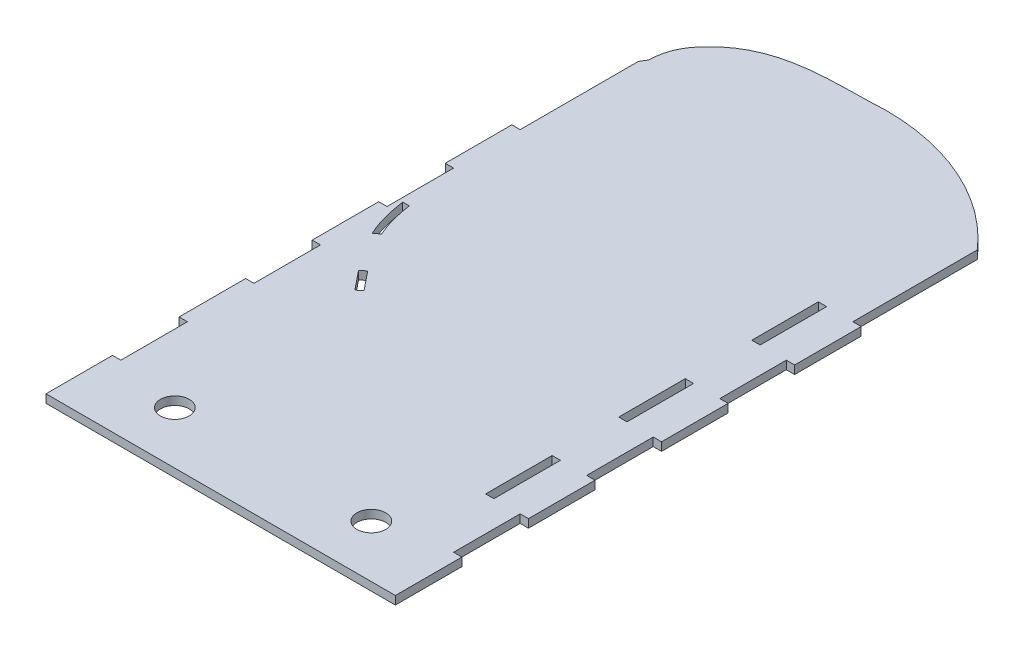
SolidWorks part; units mm, degrees
ref_plane "Front Plane" through (0, 0, 0) normal (0, 0, 1) x (1, 0, 0)
ref_plane "Top Plane" through (0, 0, 0) normal (0, 1, 0) x (1, 0, 0)
ref_plane "Right Plane" through (0, 0, 0) normal (1, 0, 0) x (0, 0, -1)
sketch "Sketch2" plane through (0, 0, 0) normal (0, 1, 0) x (1, 0, 0)
  line L0 (127, 0) -> (127, 40) construction
  line L1 (0, 0) -> (254, 0)
  line L2 (0, 0) -> (0, 508)
  line L3 (0, 508) -> (254, 508)
  line L4 (254, 0) -> (254, 508)
  line L5 (112, 0) -> (112, 40) construction
  line L6 (70.0293, 132.7246) -> (75.0014, 133.2514) construction
  line L8 (3.0464, 262.9295) -> (8.0974, 262.9295)
  line L9 (12.0177, 230.6311) -> (16.1196, 233.6878)
  line L10 (63.9635, 154.4733) -> (68.5195, 156.533) construction
  line L11 (31.3299, 200.9155) -> (35.2571, 204.0102)
  line L12 (42.9806, 186.4099) -> (46.8891, 189.5281)
  circle A0 centre (52, 40) radius 11
  circle A1 centre (202, 40) radius 11
  spline S0 degree 3 poles (0, 358) (10.2414, 318.2744) (-10.3205, 225.9555) (70.6512, 174.3118) (75.0014, 133.2514) knots 0 0 0 0 0.517006 1 1 1 1 construction
  spline S1 degree 3 poles (57.0275, 368.1055) (60.011, 340.8516) (38.8621, 298.2828) (61.0822, 235.4033) (84.5865, 206.7018) (104.9746, 198.8412) knots 0 0 0 0 0.426438 0.676001 1 1 1 1 construction
  spline S2 degree 1 poles (-4.8417, 356.7518) (70.0293, 132.7246) knots 0 0 1 1 construction
  spline S3 degree 3 poles (-4.8417, 356.7518) (-4.2453, 354.4384) (-3.2098, 349.8001) (-1.6146, 340.1963) (-0.4104, 327.7832) (0.2492, 312.4005) (0.7261, 291.8409) (1.4026, 275.812) (2.8811, 264.0829) (3.206, 261.7747) (3.5674, 259.4757) (3.9542, 257.1833) (4.5302, 254.1018) (5.5014, 249.6086) (6.6895, 245.0428) (8.2086, 240.135) (9.6429, 236.1559) (11.2633, 232.2426) (12.5555, 229.4544) (14.3601, 225.8497) (18.1885, 218.946) (23.3984, 211.2859) (29.2816, 203.4962) (32.93, 198.8824) (36.8298, 194.0373) (40.7355, 189.2215) (46.6866, 181.7864) (53.9965, 172.1125) (59.9683, 162.643) (63.1245, 156.3309) (64.1438, 154.0765) (64.4933, 153.279) (64.8362, 152.4792) (65.7137, 150.3629) (66.7102, 147.6655) (67.6191, 144.7625) (68.2641, 142.4625) (68.8611, 140.0122) (69.3531, 137.5307) (69.7433, 135.1238) (69.9343, 133.621) (70.0293, 132.7246) knots 0 0 0 0 0.03125 0.0625 0.125 0.1875 0.25 0.371368 0.378402 0.392471 0.399505 0.406539 0.420608 0.4375 0.462351 0.477976 0.5 0.513677 0.529302 0.537114 0.5625 0.625 0.649179 0.680429 0.696054 0.724459 0.755709 0.8125 0.875 0.898852 0.904562 0.907417 0.910272 0.915981 0.9375 0.948072 0.955885 0.96875 0.980913 0.988548 1 1 1 1 only from (0, 317.7537) to (70.0293, 132.7246) construction
  spline S4 degree 1 poles (35.2571, 204.0102) (46.8891, 189.5281) knots 0 0 1 1
  spline S5 degree 1 poles (31.3299, 200.9155) (42.9806, 186.4099) knots 0 0 1 1
  spline S6 degree 3 poles (3.0464, 262.9295) (4.6075, 251.8412) (7.2857, 240.8284) (12.0177, 230.6311) knots 0 0 0 0 1 1 1 1
  spline S7 degree 3 poles (8.0974, 262.9295) (9.5523, 252.911) (11.965, 242.952) (16.1196, 233.6878) knots 0 0 0 0 1 1 1 1
  spline S8 degree 3 poles (68.5195, 156.533) (70.3934, 152.3928) (73.1628, 144.7538) (74.6292, 136.7727) (75.0014, 133.2514) knots 0 0 0 0 0.562151 1 1 1 1 construction
  spline S9 degree 3 poles (63.9635, 154.4733) (65.5406, 150.9864) (68.1883, 143.8779) (69.6381, 136.4314) (70.0293, 132.7246) knots 0 0 0 0 0.506681 1 1 1 1 construction
  dimension "D3" = 22
  dimension "D1" = 508
  dimension "D2" = 254
  dimension "D4" = 40
  dimension "D5" = 15
  dimension "D6" = 60
  dimension "D7" = 150
  dimension "D8" = 5
extrude "Boss-Extrude1" add sketch "Sketch2" along normal blind 6.35
sketch "Sketch3" plane through (0, 6.35, 0) normal (0, 1, 0) x (1, 0, 0)
  line L0 (127, 508) -> (127, 338.6667) construction
  line L1 (254, 508) -> (0, 508) construction
  line L2 (127, 338.6667) -> (127, 169.3333) construction
  line L3 (127, 169.3333) -> (127, 0) construction
  line L4 (0, 0) -> (254, 0) construction
  line L5 (254, 0) -> (254, 508) construction
  line L6 (254, 508) -> (127, 508)
  line L7 (254, 450.6701) -> (254, 508)
  arc A1 (127, 508) -> (254, 450.6701) centre (127, 338.6667) cw
extrude "Cut-Extrude1" cut sketch "Sketch3" against normal up to next
sketch "Sketch5" plane through (0, 6.35, 0) normal (0, 1, 0) x (1, 0, 0)
  line L0 (254, 450.6701) -> (0, 450.6701) construction
  line L1 (0, 508) -> (0, 0) construction
  line L2 (3, 450.6701) -> (0, 445.8071)
  line L3 (0, 508) -> (0, 445.8071)
  line L6 (0, 508) -> (0, 526.7662)
  line L7 (0, 526.7662) -> (127, 526.7662)
  line L8 (127, 508) -> (127, 526.7662)
  circle A0 centre (45, 450.6701) radius 22 construction
  arc A2 (16.9934, 481.9692) -> (3, 450.6701) centre (45, 450.6701) ccw
  circle A3 centre (45, 450.6701) radius 42 construction
  spline S0 degree 3 poles (16.9934, 481.9692) (44.7711, 511.7661) (91.2093, 505.8566) (127, 508) knots 0 0 0 0 1 1 1 1
  dimension "D1" = 44
  dimension "D3" = 45
  dimension "D2" = 20
extrude "Cut-Extrude2" cut sketch "Sketch5" against normal up to next
sketch "Sketch7" plane through (0, 0, 0) normal (0, -1, 0) x (1, 0, 0)
  line L1 (254, 0) -> (260.35, 0)
  line L2 (254, 0) -> (254, -50.8)
  line L3 (254, -50.8) -> (260.35, -50.8)
  line L4 (260.35, 0) -> (260.35, -50.8)
  line L5 (0, 0) -> (-6.35, 0)
  line L6 (0, 0) -> (0, -50.8)
  line L7 (0, -50.8) -> (-6.35, -50.8)
  line L8 (-6.35, 0) -> (-6.35, -50.8)
  dimension "D1" = 6.35
  dimension "D2" = 50.8
  dimension "D3" = 6.35
  dimension "D4" = 50.8
extrude "Boss-Extrude2" add sketch "Sketch7" against normal up to surface (6.35 mm away) up to face at (9.7017, 6.35, -247.9266)
pattern_linear "LPattern1" count 4 spacing 101.6 along (0, 0, -1) of "Boss-Extrude2"
sketch "Sketch8" plane through (0, 6.35, 0) normal (0, 1, 0) x (1, 0, 0)
  line L0 (254, 152.4) -> (254, 203.2) construction
  line L5 (234, 152.4) -> (227.65, 152.4)
  line L7 (234, 152.4) -> (234, 101.6)
  line L9 (234, 101.6) -> (227.65, 101.6)
  line L10 (227.65, 152.4) -> (227.65, 101.6)
  line L11 (254, 101.6) -> (260.35, 101.6) construction
  line L12 (260.35, 101.6) -> (260.35, 152.4) construction
  dimension "D1" = 20
extrude "Cut-Extrude3" cut sketch "Sketch8" against normal up to next
pattern_linear "LPattern2" count 3 spacing 101.6 along (0, 0, -1) of "Cut-Extrude3"
sketch "Slider" plane through (0, 6.35, 6.35) normal (0, 1, 0) x (1, 0, 0)
  line L0 (0, 452.1571) -> (0, 361.95) construction
  line L6 (54.1176, 177.8402) -> (58.2442, 180.6634) construction
  spline S0 degree 3 poles (0, 364.2407) (10.0932, 324.5031) (-6.7408, 249.3382) (44.5453, 200.6868) (58.2442, 180.6634) knots 0 0 0 0 0.63201 1 1 1 1 construction
  spline S1 degree 3 poles (57.0275, 368.1055) (60.011, 340.8516) (38.8621, 298.2828) (61.0822, 235.4033) (84.5865, 206.7018) (104.9746, 198.8412) knots 0 0 0 0 0.426438 0.676001 1 1 1 1 construction
  spline S2 degree 1 poles (-4.8461, 363.0098) (54.1176, 177.8402) knots 0 0 1 1 construction
  spline S3 degree 3 poles (-4.8461, 363.0098) (-4.3659, 361.1191) (-3.5097, 357.3301) (-2.1229, 349.5349) (-0.9477, 339.5089) (-0.1716, 327.1083) (0.3662, 310.2426) (0.7835, 288.8153) (2.7416, 267.6076) (6.4419, 251.188) (10.6067, 239.2328) (16.4686, 227.9252) (23.4848, 217.3517) (31.2063, 207.235) (39.1962, 197.3973) (45.7189, 189.2885) (50.658, 182.7615) (52.9812, 179.5011) (54.1176, 177.8402) knots 0 0 0 0 0.03125 0.0625 0.125 0.1875 0.25 0.375 0.5 0.5625 0.625 0.6875 0.75 0.8125 0.875 0.9375 0.96875 1 1 1 1 only from (0, 321.3493) to (54.1176, 177.8402) construction
  point P3 (54.3917, 175.0417)
  point P4 (29.6816, 133.6685)
  point P6 (25.3244, 135.6756)
  point P7 (21.5394, 135.5229)
  point P9 (39.4971, 156.8777)
  point P14 (48.3521, 164.8172)
  point P22 (25.7297, 133.6685)
  point P24 (28.7283, 133.1056)
  point P26 (0, 0)
  point P28 (38.3521, 159.023)
  point P29 (21.6318, 141.6479)
  dimension "D8" = 5
